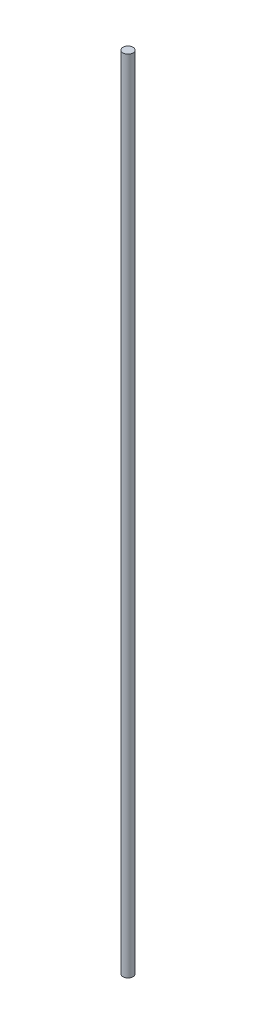
SolidWorks part; units mm, degrees
ref_plane "Front Plane" through (0, 0, 0) normal (0, 0, 1) x (1, 0, 0)
ref_plane "Top Plane" through (0, 0, 0) normal (0, 1, 0) x (1, 0, 0)
ref_plane "Right Plane" through (0, 0, 0) normal (1, 0, 0) x (0, 0, -1)
sketch "Sketch1" plane through (0, 0, 0) normal (0, 1, 0) x (1, 0, 0)
  circle A0 centre (0, 0) radius 1.5875
  dimension "D1" = 3.175
extrude "Boss-Extrude1" add sketch "Sketch1" along normal blind 254
ref_plane "Plane1" through (0, 127, 0) normal (0, 1, 0) x (1, 0, 0)
